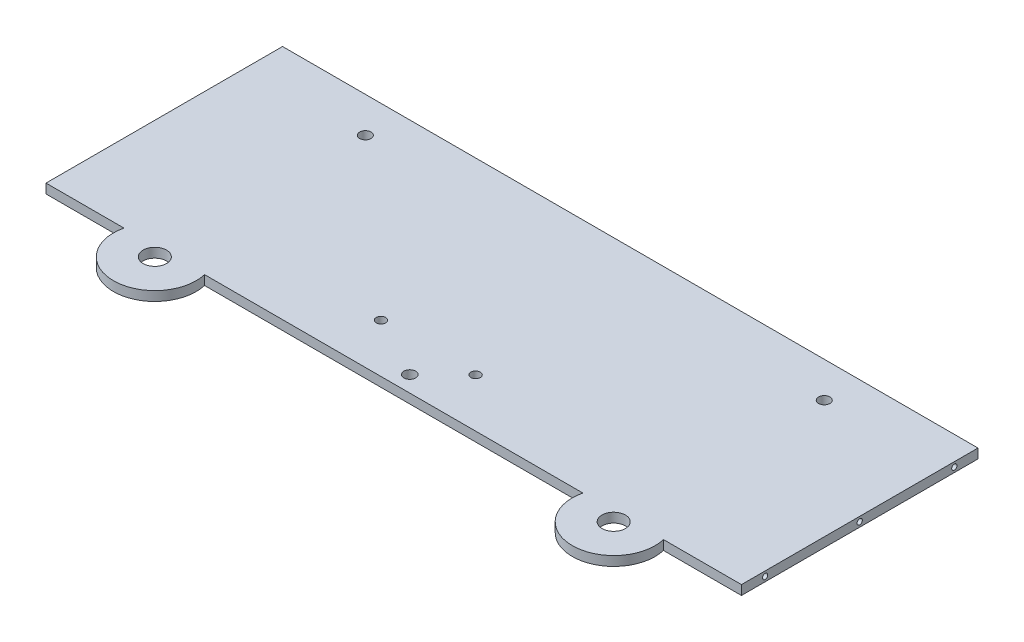
SolidWorks part; units mm, degrees
ref_plane "Front Plane" through (0, 0, 0) normal (0, 0, 1) x (1, 0, 0)
ref_plane "Top Plane" through (0, 0, 0) normal (0, 1, 0) x (1, 0, 0)
ref_plane "Right Plane" through (0, 0, 0) normal (1, 0, 0) x (0, 0, -1)
sketch "Sketch1" plane through (0, 0, 0) normal (0, 1, 0) x (1, 0, 0)
  line L0 (0, 0) -> (0, -63.5) construction
  line L1 (-186.69, -63.5) -> (186.69, -63.5)
  line L2 (-186.69, -63.5) -> (-186.69, 63.5)
  line L3 (-186.69, 63.5) -> (186.69, 63.5)
  line L4 (186.69, -63.5) -> (186.69, 63.5)
  line L5 (-186.69, -63.5) -> (186.69, 63.5) construction
  line L6 (-186.69, 63.5) -> (186.69, -63.5) construction
  line L7 (-123.19, -68.58) -> (-123.19, -63.5) construction
  line L8 (123.19, -68.58) -> (123.19, -63.5) construction
  line L9 (17.78, -37.338) -> (17.78, -63.5) construction
  circle A0 centre (-123.19, -68.58) radius 22.225
  circle A1 centre (123.19, -68.58) radius 22.225
  circle A2 centre (-123.19, -68.58) radius 6.2865
  circle A3 centre (123.19, -68.58) radius 6.2865
  circle A4 centre (-123.19, 44.45) radius 3.048
  circle A5 centre (123.19, 44.45) radius 3.048
  circle A6 centre (-33.02, -37.338) radius 2.54
  circle A7 centre (17.78, -37.338) radius 2.54
  circle A8 centre (0, -54.864) radius 3.175
  point P0 (0, 0)
  point P17 (123.19, 44.45)
  point P21 (-123.19, 44.45)
  dimension "D3" = 44.45
  dimension "D4" = 44.45
  dimension "D8" = 12.573
  dimension "D9" = 12.573
  dimension "D11" = 6.096
  dimension "D12" = 6.096
  dimension "D16" = 5.08
  dimension "D17" = 5.08
  dimension "D20" = 6.35
  dimension "D1" = 373.38
  dimension "D2" = 127
  dimension "D5" = 5.08
  dimension "D6" = 123.19
  dimension "D7" = 123.19
  dimension "D10" = 107.95
  dimension "D13" = 26.162
  dimension "D14" = 17.78
  dimension "D15" = 50.8
  dimension "D18" = 8.636
extrude "Boss-Extrude1" add sketch "Sketch1" along normal blind 5.0749 contours L1 A0 | L1 A1 | L3 L4 L1 L2 | A2 | A3 region at (-123.19, 0, 76.2008) region at (123.19, 0, 76.2008)
extrude "Cut-Extrude1" cut sketch "Sketch1<5>" along normal through all contours A3 | A2
sketch "Sketch1<5>" plane through (0, 0, 0) normal (0, 1, 0) x (1, 0, 0) same geometry as "Sketch1"
extrude "Cut-Extrude2" cut sketch "Sketch1<7>" along normal through all and the other way through all contours A4 | A5
sketch "Sketch1<7>" plane through (0, 0, 0) normal (0, 1, 0) x (1, 0, 0) same geometry as "Sketch1"
extrude "Cut-Extrude3" cut sketch "Sketch1<8>" along normal through all contours A7 | A6 | A8
sketch "Sketch1<8>" plane through (0, 0, 0) normal (0, 1, 0) x (1, 0, 0) same geometry as "Sketch1"
sketch "Sketch2" plane through (186.69, 0, 0) normal (1, 0, 0) x (0, 0, -1)
  line L0 (63.5, 2.5375) -> (-63.5, 2.5375) construction
  line L1 (63.5, 5.0749) -> (63.5, 0) construction
  line L2 (-63.5, 5.0749) -> (-63.5, 0) construction
  circle A0 centre (0, 2.5375) radius 1.4224
  circle A1 centre (-50.8, 2.5375) radius 1.4224
  circle A2 centre (50.8, 2.5375) radius 1.4224
  dimension "D1" = 50.8
  dimension "D2" = 50.8
extrude "Cut-Extrude4" cut sketch "Sketch2" against normal blind 12.7
sketch "Sketch3" plane through (-186.69, 0, 0) normal (-1, 0, 0) x (0, 0, 1)
  line L0 (-63.5, 2.5375) -> (63.5, 2.5375) construction
  line L1 (-63.5, 5.0749) -> (-63.5, 0) construction
  line L2 (63.5, 5.0749) -> (63.5, 0) construction
  circle A0 centre (-50.8, 2.5375) radius 1.4224
  circle A1 centre (0, 2.5375) radius 1.4224
  dimension "D1" = 12.7
  dimension "D2" = 50.8
extrude "Cut-Extrude5" cut sketch "Sketch3" against normal blind 12.7
